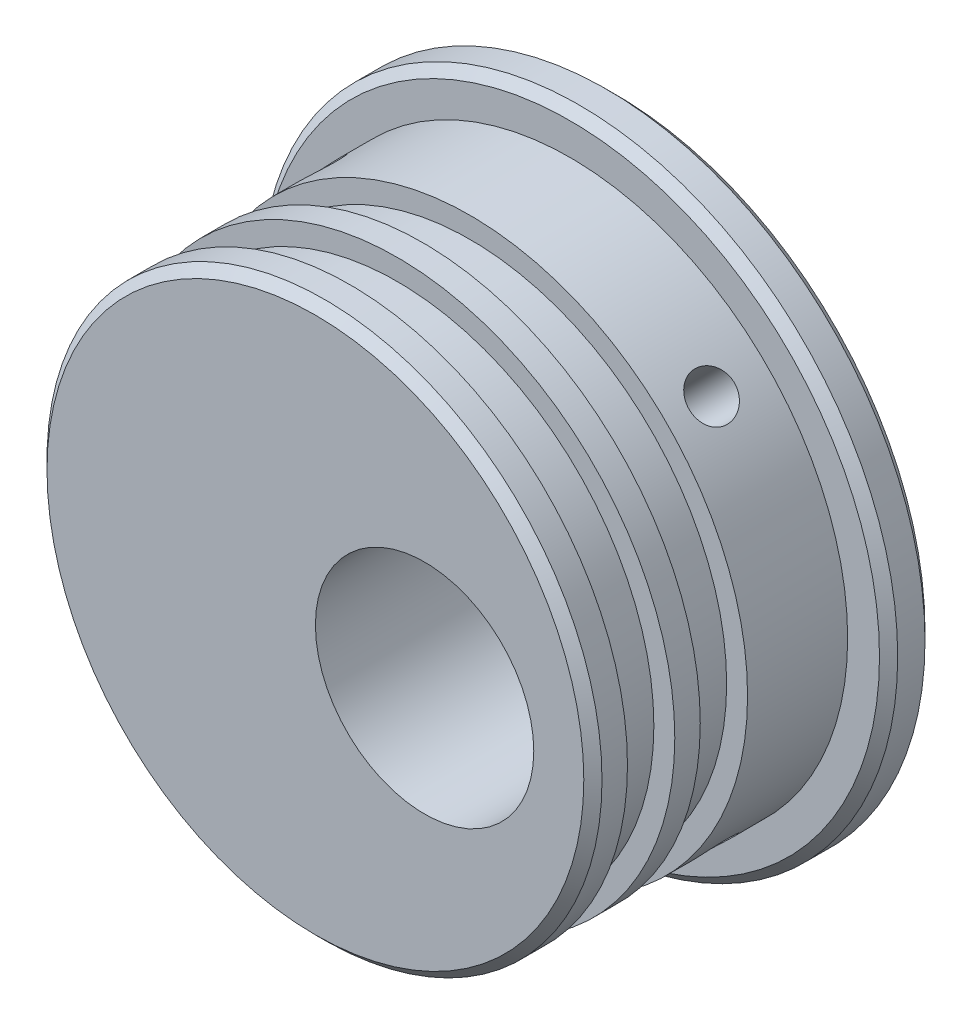
SolidWorks part; units mm, degrees
ref_plane "Спереди" through (0, 0, 0) normal (0, 0, 1) x (1, 0, 0)
ref_plane "Сверху" through (0, 0, 0) normal (0, 1, 0) x (1, 0, 0)
ref_plane "Справа" through (0, 0, 0) normal (1, 0, 0) x (0, 0, -1)
other "Configuration Table"
sketch "Эскиз1" plane through (0, 0, 0) normal (0, 0, 1) x (1, 0, 0)
  circle A0 centre (0, 0) radius 17.5
  circle A1 centre (0, 0) radius 15.25
  circle A2 centre (0, 0) radius 14.1
  point P6 (0, 0)
  point P7 (-6.9123, -1.7917)
  point P8 (-3.7492, -1.8801)
  point P9 (0, 0)
  point P10 (0, 0)
  point P11 (-1.8912, -1.7474)
  point P12 (6.7575, 1.1944)
  point P13 (0, 0)
  dimension "D1" = 35
  dimension "D2" = 30.5
  dimension "D3" = 28.2
extrude "Бобышка-Вытянуть1" add sketch "Эскиз1" against normal blind 2.5 contours A0 A1 | A1 A2 | A2 region at (-17.005, 0, 0) region at (-14.8187, 0, 0) region at (0, 0, 0)
extrude "Бобышка-Вытянуть2" add sketch "Эскиз1<3>" along normal blind 14 contours A1 A2 | A2 region at (-14.8187, 0, 0) region at (0, 0, 0)
sketch "Эскиз1<3>" plane through (0, 0, 0) normal (0, 0, 1) x (1, 0, 0) same geometry as "Эскиз1"
extrude "Вырез-Вытянуть1" cut sketch "Эскиз1<4>" along normal blind 2.6 from offset 5.5 contours A1 A2 region at (-14.8187, 0, 0)
sketch "Эскиз1<4>" plane through (0, 0, 0) normal (0, 0, 1) x (1, 0, 0) same geometry as "Эскиз1"
extrude "Вырез-Вытянуть2" cut sketch "Эскиз1<5>" along normal blind 2.6 from offset 9.5 contours A1 A2 region at (-14.8187, 0, 0)
sketch "Эскиз1<5>" plane through (0, 0, 0) normal (0, 0, 1) x (1, 0, 0) same geometry as "Эскиз1"
chamfer "Фаска1" distance 0.5 angle 45 3 edges at (15.25, 0, 14) (17.5, 0, 0) (17.5, 0, -2.5)
sketch "Эскиз2" plane through (0, 0, -2.5) normal (0, 0, -1) x (-1, 0, 0)
  circle A0 centre (-6, 0) radius 6
  point P3 (0, 0)
  point P4 (-5.9833, 0.2876)
  dimension "D1" = 12
  dimension "D2" = 6
sketch "Эскиз3" plane through (0, 0, 0) normal (0, 1, 0) x (1, 0, 0)
  line L0 (0, 0) -> (0, 5.0181)
ref_plane "Плоскость1" through (0, 0, 0) normal (0.7071, 0.7071, 0) x (0, 0, -1)
extrude "Вырез-Вытянуть5" cut sketch "Эскиз2" against normal through all
sketch "Эскиз4" plane through (0, 0, 0) normal (0.7071, 0.7071, 0) x (0, 0, -1)
  circle A0 centre (-3, 0) radius 1.25
  dimension "D1" = 2.5
  dimension "D2" = 3
extrude "Вырез-Вытянуть6" cut sketch "Эскиз4" along normal through all from offset 10
pattern_circular "Круговой массив1" count 4 every 90 about axis through (0, 0, 0) along (0, 0, -1) of "Вырез-Вытянуть6"
